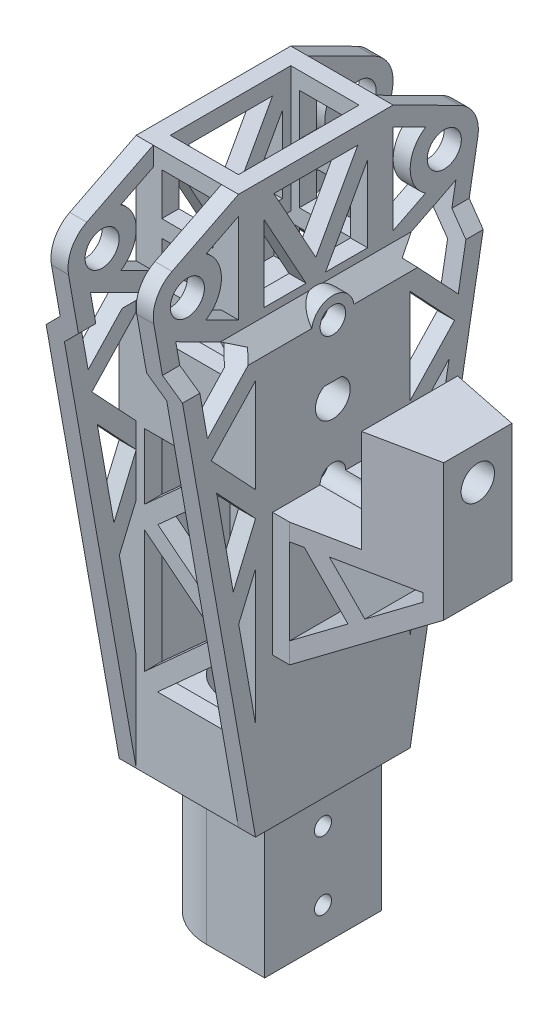
SolidWorks part; units mm, degrees
other "Markup1"
sketch "Sketch125" plane through (39.6875, -63.7385, 30.2705) normal (0.4776, -0.0046, 0.8786) x (0.8777, 0.0477, -0.4769)
material "Oynx"
ref_plane "Front Plane" through (0, 0, 0) normal (0, 0, 1) x (1, 0, 0)
ref_plane "Top Plane" through (0, 0, 0) normal (0, 1, 0) x (1, 0, 0)
ref_plane "Right Plane" through (0, 0, 0) normal (1, 0, 0) x (0, 0, -1)
sketch "Sketch1" plane through (0, 0, 0) normal (0, 1, 0) x (1, 0, 0)
  line L1 (-9.525, -14.3954) -> (9.525, -14.3954)
  line L2 (-9.525, -14.3954) -> (-9.525, 14.3954)
  line L3 (-9.525, 14.3954) -> (9.525, 14.3954)
  line L4 (9.525, -14.3954) -> (9.525, 14.3954)
  line L5 (-9.525, -14.3954) -> (9.525, 14.3954) construction
  line L6 (-9.525, 14.3954) -> (9.525, -14.3954) construction
  point P0 (0, 0)
  dimension "D1" = 28.7909
  dimension "D2" = 19.05
extrude "Boss-Extrude1" add sketch "Sketch1" along normal mid plane 127.4771 contours L3 L4 L1 L2
sketch "Sketch2" plane through (0, -63.7385, 0) normal (0, -1, 0) x (1, 0, 0)
  line L1 (-9.525, -9.525) -> (9.525, -9.525)
  line L2 (-9.525, -9.525) -> (-9.525, 9.525)
  line L3 (-9.525, 9.525) -> (9.525, 9.525)
  line L4 (9.525, -9.525) -> (9.525, 9.525)
  line L5 (-9.525, -9.525) -> (9.525, 9.525) construction
  line L6 (-9.525, 9.525) -> (9.525, -9.525) construction
  point P0 (0, 0)
  dimension "D1" = 19.05
extrude "Cut-Extrude1" cut sketch "Sketch2" against normal blind 25.4 flip side to cut contours L3 L4 L1 L2
sketch "Sketch30" plane through (0, 0, 0) normal (0, 0, 1) x (1, 0, 0)
  line L0 (9.525, -38.3385) -> (-9.525, -38.3385) construction
  line L1 (-9.525, 63.7385) -> (-12.7, 63.7385)
  line L2 (-9.525, 63.7385) -> (-9.525, -38.3385)
  line L3 (-9.525, -38.3385) -> (-12.7, -38.3385)
  line L4 (-12.7, 63.7385) -> (-12.7, -38.3385)
  line L6 (9.525, 63.7385) -> (12.7, 63.7385)
  line L7 (9.525, 63.7385) -> (9.525, -38.3385)
  line L8 (9.525, -38.3385) -> (12.7, -38.3385)
  line L9 (12.7, 63.7385) -> (12.7, -38.3385)
  dimension "D1" = 3.175
extrude "Boss-Extrude8" add sketch "Sketch30" along normal up to surface and the other way up to surface up to face at (0, 12.7, 14.3954) other way up to face at (0, 12.7, -14.3954)
sketch "Sketch115" plane through (0, -38.3385, 0) normal (0, -1, 0) x (1, 0, 0)
  line L1 (-10.8585, -10.8585) -> (10.8585, -10.8585)
  line L2 (-10.8585, -10.8585) -> (-10.8585, 10.8585)
  line L3 (-10.8585, 10.8585) -> (10.8585, 10.8585)
  line L4 (10.8585, -10.8585) -> (10.8585, 10.8585)
  line L5 (-10.8585, -10.8585) -> (10.8585, 10.8585) construction
  line L6 (-10.8585, 10.8585) -> (10.8585, -10.8585) construction
  line L11 (9.525, 9.525) -> (-9.525, 9.525)
  line L12 (-9.525, 9.525) -> (-9.525, -9.525)
  line L13 (-9.525, -9.525) -> (9.525, -9.525)
  line L14 (9.525, -9.525) -> (9.525, 9.525)
  line L15 (9.525, 9.525) -> (-9.525, 9.525)
  line L16 (-9.525, 9.525) -> (-9.525, -9.525)
  line L17 (-9.525, -9.525) -> (9.525, -9.525)
  line L18 (9.525, -9.525) -> (9.525, 9.525)
  point P0 (0, 0)
  dimension "D1" = 21.717
  dimension "D2" = 0
extrude "Boss-Extrude13" add sketch "Sketch115" along normal up to surface (25.4 mm away) up to face at (0, -63.7385, 0)
sketch "Sketch81" plane through (0, -63.7385, 0) normal (0, -1, 0) x (1, 0, 0)
  line L0 (10.8585, 10.8585) -> (-10.8585, 10.8585) construction
  line L1 (0, 10.8585) -> (-10.8585, 10.8585)
  line L8 (-10.8585, 10.8585) -> (-10.8585, 0)
  line L14 (-10.8585, 0) -> (-10.8585, -10.8585)
  line L15 (-10.8585, -10.8585) -> (0, -10.8585)
  arc A2 (0, 10.8585) -> (0, -10.8585) centre (0, 0) ccw
  arc A3 (0, -10.8585) -> (0, 10.8585) centre (0, 0) ccw construction
  line M22 (-10.8585, -10.8585) -> (10.8585, -10.8585)
  line M24 (10.8585, 10.8585) -> (-10.8585, 10.8585)
  line M25 (-10.8585, 10.8585) -> (-10.8585, -10.8585)
extrude "Cut-Extrude37" cut sketch "Sketch81" against normal up to surface (25.4 mm away) contours A2 M24 M25 | A2 M25 M22 region at (-8.4331, -63.7385, 8.4331) region at (-8.4331, -63.7385, -8.4331) up to face at (0, -38.3385, 0)
sketch "Sketch62" plane through (12.7, 0, 0) normal (1, 0, 0) x (0, 0, -1)
  line L0 (0, 25.1615) -> (0, -38.3385) construction
  line L1 (-14.3955, -38.3385) -> (14.3955, -38.3385) construction
  line L2 (1.651, 27.9475) -> (-1.651, 27.9475)
  arc A0 (-1.651, 27.9475) -> (1.651, 27.9475) centre (0, 25.1615) ccw
  dimension "D2" = 6.477
  dimension "D1" = 63.5
  dimension "D3" = 3.302
extrude "Cut-Extrude31_D-ShaftHole" cut sketch "Sketch62" against normal through all
sketch "Sketch22" plane through (0, -63.7385, 0) normal (0, -1, 0) x (1, 0, 0)
  line L6 (0, -7.6835) -> (7.6835, -7.6835)
  line L7 (7.6835, -7.6835) -> (7.6835, 7.6835)
  line L8 (7.6835, 7.6835) -> (0, 7.6835)
  line L9 (0, -7.6835) -> (7.6835, -7.6835)
  line L10 (7.6835, -7.6835) -> (7.6835, 7.6835)
  line L11 (7.6835, 7.6835) -> (0, 7.6835)
  arc A3 (0, 7.6835) -> (0, -7.6835) centre (0, 0) ccw
  arc A4 (0, 7.6835) -> (0, -7.6835) centre (0, 0) ccw
  dimension "D1" = 3.175
extrude "Cut-Extrude4_BottomHole" cut sketch "Sketch22" against normal blind 38.1
sketch "Sketch26" plane through (0, 0, 0) normal (1, 0, 0) x (0, 0, -1)
  line L0 (-14.3955, 63.7385) -> (-14.3955, -38.3385) construction
  line L1 (0, 65.1622) -> (0, -27.4319) construction
  line L2 (-14.3955, 63.7385) -> (-26.7765, 57.5038)
  line L3 (-14.3955, 39.926) -> (-29.6181, 47.5918) construction
  line L4 (-23.9205, 51.8323) -> (-14.3955, 51.8323) construction
  line L5 (-14.3955, 63.7385) -> (-14.3955, 51.8323) construction
  line L6 (-14.3955, 51.8323) -> (-14.3955, 39.926) construction
  line L7 (-14.3955, 43.4809) -> (-20.4368, 46.5232)
  line L8 (-17.4161, 45.002) -> (-18.8441, 42.1663) construction
  line L9 (-14.3955, 60.1837) -> (-20.4368, 57.1414)
  line L10 (-17.4161, 58.6626) -> (-18.8441, 61.4983) construction
  line L11 (-14.3955, 63.7385) -> (-14.3955, 60.1837)
  line L12 (-14.3955, 43.4809) -> (-14.3955, 39.926) construction
  line L13 (-30.1731, 50.7246) -> (-14.3955, -38.3385)
  line L14 (-14.3955, 43.4809) -> (-14.3955, -38.3385)
  line L15 (14.3955, 43.4809) -> (14.3955, 39.926) construction
  line L16 (17.4161, 58.6626) -> (18.8441, 61.4983) construction
  line L17 (17.4161, 45.002) -> (18.8441, 42.1663) construction
  line L18 (14.3955, 51.8323) -> (14.3955, 39.926) construction
  line L19 (14.3955, 63.7385) -> (14.3955, 51.8323) construction
  line L20 (23.9205, 51.8323) -> (14.3955, 51.8323) construction
  line L21 (14.3955, 39.926) -> (29.6181, 47.5918) construction
  line L22 (14.3955, 43.4809) -> (14.3955, -38.3385)
  line L23 (30.1731, 50.7246) -> (14.3955, -38.3385)
  line L24 (14.3955, 63.7385) -> (14.3955, 60.1837)
  line L25 (14.3955, 60.1837) -> (20.4368, 57.1414)
  line L26 (14.3955, 43.4809) -> (20.4368, 46.5232)
  line L27 (14.3955, 63.7385) -> (26.7765, 57.5038)
  arc A0 (-26.7765, 57.5038) -> (-30.1731, 50.7246) centre (-23.9205, 51.8323) ccw
  circle A1 centre (-23.9205, 51.8323) radius 3.175
  arc A2 (-20.4368, 46.5232) -> (-20.4368, 57.1414) centre (-23.9205, 51.8323) ccw
  arc A3 (20.4368, 46.5232) -> (20.4368, 57.1414) centre (23.9205, 51.8323) cw
  circle A4 centre (23.9205, 51.8323) radius 3.175
  arc A5 (26.7765, 57.5038) -> (30.1731, 50.7246) centre (23.9205, 51.8323) cw
  dimension "D3" = 6.35
  dimension "D4" = 12.7
  dimension "D1" = 11.9062
  dimension "D2" = 9.525
  dimension "D5" = 3.175
sketch "Sketch116" plane through (10.8585, 0, 0) normal (1, 0, 0) x (0, 0, -1)
  line L0 (0, -57.3885) -> (0, -44.6885) construction
  line L1 (0, -44.6885) -> (0, -38.3385) construction
  line L2 (-14.3955, -38.3385) -> (14.3955, -38.3385) construction
  line L3 (0, -57.3885) -> (0, -63.7385) construction
  line L4 (10.8585, -63.7385) -> (-10.8585, -63.7385) construction
  circle A0 centre (0, -44.6885) radius 1.5875
  circle A1 centre (0, -57.3885) radius 1.5875
  dimension "D2" = 3.175
  dimension "D1" = 12.7
extrude "Cut-Extrude65" cut sketch "Sketch116" against normal through all
extrude "Boss-Extrude3_\"Fins\"" add sketch "Sketch26" along normal up to surface (12.7 mm away) and the other way up to surface (12.7 mm away) contours L7 A2 L9 L11 L2 A0 L13 L14 A1 | A5 L27 L24 L25 A3 L26 L22 L23 A4 region at (0, 23.6902, 19.9871) region at (0, 23.6902, -19.9871) up to face at (12.7, 24.9352, 0) other way up to face at (-12.7, 24.9352, 0)
sketch "Sketch27" plane through (0, 63.7385, 0) normal (0, 1, 0) x (1, 0, 0)
  line L0 (-12.7, -14.3955) -> (12.7, -14.3955) construction
  line L1 (-6.35, -14.3955) -> (6.35, -14.3955)
  line L2 (-6.35, -14.3955) -> (-6.35, -30.2704)
  line L3 (-6.35, -30.2704) -> (6.35, -30.2704)
  line L4 (6.35, -14.3955) -> (6.35, -30.2704)
  line L5 (-12.7, -30.2704) -> (12.7, -30.2704) construction
  line L6 (-6.35, -22.3329) -> (-12.7, -22.333) construction
  line L7 (-12.7, -14.3955) -> (-12.7, -26.7765) construction
  line L8 (6.35, -22.3329) -> (12.7, -22.3329) construction
  line L9 (12.7, -26.7765) -> (12.7, -14.3955) construction
  line L10 (-12.7, 0) -> (12.7, 0) construction
  line L11 (-12.7, -14.3955) -> (-12.7, 14.3955) construction
  line L12 (12.7, -14.3955) -> (12.7, 14.3955) construction
  line L13 (6.35, 22.3329) -> (12.7, 22.3329) construction
  line L14 (-6.35, 22.3329) -> (-12.7, 22.333) construction
  line L15 (6.35, 14.3955) -> (6.35, 30.2704)
  line L16 (-6.35, 30.2704) -> (6.35, 30.2704)
  line L17 (-6.35, 14.3955) -> (-6.35, 30.2704)
  line L18 (-6.35, 14.3955) -> (6.35, 14.3955)
  dimension "D1" = 6.35
extrude "Cut-Extrude7" cut sketch "Sketch27" against normal through all
sketch "Sketch31" plane through (0, 0, 14.3954) normal (0, 0, 1) x (1, 0, 0)
  line L0 (-9.525, -38.3385) -> (-9.525, 37.1309)
  line L1 (-6.35, -38.3385) -> (-12.7, -38.3385) construction
  line L2 (-9.525, 37.1309) -> (-6.35, 40.3059)
  line L3 (-6.35, -38.3385) -> (-6.35, 50.7246) construction
  line L4 (-6.35, 40.3059) -> (-6.35, -38.3385)
  line L5 (-6.35, -38.3385) -> (-9.525, -38.3385)
  line L6 (6.35, -38.3385) -> (6.35, 40.3059)
  line L7 (6.35, 50.7246) -> (6.35, -38.3385) construction
  line L8 (6.35, 40.3059) -> (9.525, 37.1309)
  line L9 (9.525, 37.1309) -> (9.525, -38.3385)
  line L10 (12.7, -38.3385) -> (6.35, -38.3385) construction
  line L11 (9.525, -38.3385) -> (6.35, -38.3385)
  line L12 (9.525, 37.1309) -> (6.35, 37.1309) construction
  line L13 (-9.525, 37.1309) -> (-6.35, 37.1309) construction
  line L14 (-6.35, 40.3059) -> (6.35, 40.3059) construction
  dimension "D1" = 3.175
  dimension "D2" = 45
  dimension "D3" = 45
  dimension "D4" = 3.175
extrude "Cut-Extrude13" cut sketch "Sketch31" along normal through all
extrude "Cut-Extrude16" cut sketch "Sketch31<2>" against normal through all from surface starting at face at (0, 38.7882, -14.3954)
sketch "Sketch31<2>" plane through (0, 0, 14.3954) normal (0, 0, 1) x (1, 0, 0) same geometry as "Sketch31"
sketch "Sketch53" plane through (0, 0, 0) normal (0, 0, 1) x (1, 0, 0)
  line L0 (12.7, 38.446) -> (9.525, 41.621)
  line L1 (12.7, -38.3385) -> (12.7, 50.7246) construction
  line L2 (9.525, 41.621) -> (9.525, 63.7385)
  line L3 (6.35, 63.7385) -> (12.7, 63.7385) construction
  line L4 (9.525, 63.7385) -> (12.7, 63.7385)
  line L5 (12.7, 63.7385) -> (12.7, 38.446)
  line L6 (9.525, 37.1309) -> (6.35, 40.3059) construction
  line L7 (7.9375, 38.7184) -> (10.1826, 40.9635) construction
  line L8 (9.525, 52.6798) -> (6.35, 52.6798) construction
  line L9 (6.35, 57.5038) -> (6.35, 50.7246) construction
  line L10 (0, 47.881) -> (0, -47.881) construction
  line L11 (-9.525, 52.6798) -> (-6.35, 52.6798) construction
  line L12 (-7.9375, 38.7184) -> (-10.1826, 40.9635) construction
  line L13 (-12.7, 63.7385) -> (-12.7, 38.446)
  line L14 (-9.525, 63.7385) -> (-12.7, 63.7385)
  line L15 (-9.525, 41.621) -> (-9.525, 63.7385)
  line L16 (-12.7, 38.446) -> (-9.525, 41.621)
  dimension "D1" = 3.175
extrude "Cut-Extrude30" cut sketch "Sketch53" against normal through all both and the other way through all
sketch "Sketch54" plane through (0, 0, 0) normal (1, 0, 0) x (0, 0, -1)
  line L0 (-14.3955, 43.4809) -> (-14.3955, -38.3385) construction
  line L1 (-26.0875, 45.8635) -> (-14.3955, -20.1369) construction
  line L2 (-14.3955, -38.3385) -> (-27.9979, 38.446) construction
  line L3 (-20.2415, 12.8633) -> (-23.3678, 12.3095) construction
  line L4 (-26.0779, 45.809) -> (-14.3955, 39.926)
  line L5 (-20.4368, 46.5232) -> (-14.3955, 43.4809) construction
  line L6 (-17.4161, 45.002) -> (-18.8441, 42.1663) construction
  line L7 (-26.0779, 45.809) -> (-23.346, 30.3879)
  line L8 (-23.346, 30.3879) -> (-14.3955, 39.926)
  line L9 (-14.3955, 35.2862) -> (-22.6546, 26.4849)
  line L10 (-22.6546, 26.4849) -> (-14.3955, 17.6836)
  line L11 (-14.3955, 17.6836) -> (-14.3955, 35.2862)
  line L15 (-18.525, 30.8855) -> (-20.8403, 33.0582) construction
  line L18 (-14.3955, 13.0437) -> (-21.6413, 20.7653)
  line L20 (-18.0184, 16.9045) -> (-15.7031, 19.0771) construction
  line L21 (-26.0779, 45.809) -> (-26.7765, 46.1608) construction
  line L22 (0, 43.7979) -> (0, -43.7979) construction
  line L23 (26.0779, 45.809) -> (26.7765, 46.1608) construction
  line L24 (18.0184, 16.9045) -> (15.7031, 19.0771) construction
  line L25 (18.525, 30.8855) -> (20.8403, 33.0582) construction
  line L26 (17.4161, 45.002) -> (18.8441, 42.1663) construction
  line L27 (20.2415, 12.8633) -> (23.3678, 12.3095) construction
  line L28 (26.0875, 45.8635) -> (14.3955, -20.1369) construction
  line L29 (14.3955, 43.4809) -> (14.3955, -38.3385) construction
  line L31 (14.3955, 13.0437) -> (21.6413, 20.7653)
  line L33 (14.3955, 17.6836) -> (14.3955, 35.2862)
  line L34 (22.6546, 26.4849) -> (14.3955, 17.6836)
  line L35 (14.3955, 35.2862) -> (22.6546, 26.4849)
  line L36 (23.346, 30.3879) -> (14.3955, 39.926)
  line L37 (26.0779, 45.809) -> (23.346, 30.3879)
  line L38 (26.0779, 45.809) -> (14.3955, 39.926)
  line L39 (-21.6413, 20.7653) -> (-18.5479, 3.303)
  line L40 (-18.5479, 3.303) -> (-14.3955, 13.0437)
  line L41 (-14.3955, 4.9473) -> (-17.5346, -2.4166)
  line L42 (-14.3955, 4.9473) -> (-14.3955, -20.1369)
  line L43 (-14.3955, -20.1369) -> (-17.5346, -2.4166)
  line L44 (-16.4717, 8.1734) -> (-13.551, 6.9283) construction
  line L45 (14.3955, 13.0437) -> (18.5479, 3.303)
  line L46 (18.5479, 3.303) -> (21.6413, 20.7653)
  line L47 (14.3955, -20.1369) -> (17.5346, -2.4166)
  line L48 (17.5346, -2.4166) -> (14.3955, 4.9473)
  line L49 (14.3955, 4.9473) -> (14.3955, -20.1369)
  line L50 (15.965, 1.2653) -> (18.8857, 2.5104) construction
  circle A0 centre (-23.9205, 51.8323) radius 6.35 construction
  arc A1 (-20.4368, 46.5232) -> (-20.4368, 57.1414) centre (-23.9205, 51.8323) ccw construction
  circle A2 centre (23.9205, 51.8323) radius 6.35 construction
  dimension "D1" = 3.175
extrude "Cut-Extrude31_FrontSideCutouts" cut sketch "Sketch54" against normal through all both and the other way through all contours L7 L8 L4 | L10 L11 L9 | L37 L38 L36 | L35 L33 L34 | L31 | L43 L42 L41 | L48 L49 L47 | L18 L39 L40 region at (0, 38.7077, 21.2731) region at (0, 26.4849, 17.1485) region at (0, 12.3707, -18.1949) region at (0, 26.4849, -17.1485) region at (0, 38.7077, -21.2731) region at (0, -5.8688, 15.4418) region at (0, -5.8688, -15.4418)
sketch "Sketch75" plane through (0, 0, 14.3954) normal (0, 0, 1) x (1, 0, 0)
  line L0 (9.525, -38.3385) -> (9.525, 37.1309) construction
  line L7 (9.525, 37.1309) -> (6.7298, 39.926) construction
  line L8 (-9.525, 41.621) -> (9.525, 41.621) construction
  line L9 (-6.9512, 37.4597) -> (-8.0737, 38.5822) construction
  line L14 (-6.7298, 39.926) -> (-9.525, 37.1309) construction
  line L32 (-12.7, 38.446) -> (12.7, 38.446) construction
  line L62 (6.9512, 37.4597) -> (8.0737, 38.5822) construction
  line L63 (9.525, 37.1309) -> (6.35, 40.3059) construction
  line L64 (-4.7625, 51.0923) -> (4.7625, 51.0923) construction
  line L65 (-6.35, 60.5635) -> (6.35, 60.5635) construction
  line L66 (-6.35, 60.1837) -> (-6.35, 63.7385) construction
  line L67 (6.35, 63.7385) -> (6.35, 57.5038) construction
  line L68 (0, 60.5635) -> (0, 63.7385) construction
  line L69 (6.35, 63.7385) -> (-6.35, 63.7385) construction
  line L70 (0, 41.621) -> (0, 38.446) construction
  line L71 (-4.7625, 41.621) -> (-4.7625, 60.5635) construction
  line L72 (4.7625, 60.5635) -> (4.7625, 41.621) construction
  line L73 (-4.7625, 51.0923) -> (-6.35, 51.0923) construction
  line L74 (-6.35, 50.7246) -> (-6.35, 57.5038) construction
  line L75 (4.7625, 51.0923) -> (6.35, 51.0923) construction
  line L76 (6.35, 57.5038) -> (6.35, 50.7246) construction
  line L77 (-4.7625, 52.6798) -> (4.7625, 52.6798)
  line L82 (0, 52.6798) -> (0, 49.5048) construction
  line L85 (-6.35, 40.3059) -> (-9.525, 37.1309) construction
  line L86 (7.9375, 36.4733) -> (5.9648, 38.446)
  line L87 (5.9648, 38.446) -> (-5.9648, 38.446)
  line L89 (-5.9648, 38.446) -> (-7.9375, 36.4733)
  line L90 (7.9375, 36.4733) -> (7.9375, 33.099)
  line L91 (7.9375, 33.099) -> (-7.9375, 33.099)
  line L92 (-7.9375, 33.099) -> (-7.9375, 36.4733)
  line L93 (12.7, 33.099) -> (-12.7, 33.099) construction
  line L94 (12.7, -38.3385) -> (12.7, 38.446) construction
  line L95 (-12.7, -38.3385) -> (-12.7, 38.446) construction
  line L96 (4.7625, 49.5048) -> (-4.7625, 49.5048)
  line L113 (-9.525, 37.1309) -> (-9.525, -38.3385) construction
  line L117 (-4.7625, 52.6798) -> (-4.7625, 60.5635)
  line L118 (-4.7625, 60.5635) -> (4.7625, 60.5635)
  line L124 (12.7, 25.1615) -> (-12.7, 25.1615) construction
  line L125 (12.7, -38.3385) -> (12.7, 38.446) construction
  line L126 (-12.7, -38.3385) -> (-12.7, 38.446) construction
  line L127 (0, 25.1615) -> (0, -38.3385) construction
  line L128 (9.525, -38.3385) -> (-9.525, -38.3385) construction
  line L131 (4.7625, 60.5635) -> (4.7625, 52.6798)
  line L132 (4.7625, 49.5048) -> (4.7625, 41.621)
  line L133 (4.7625, 41.621) -> (-4.7625, 41.621)
  line L134 (-4.7625, 41.621) -> (-4.7625, 49.5048)
  point P62 (0, 51.0923)
  dimension "D2" = 63.5
  dimension "D3" = 7.9375
  dimension "D4" = 3.175
  dimension "D5" = 1.5875
  dimension "D10" = 1.5875
  dimension "D11" = 1.5875
  dimension "D12" = 3.175
sketch "Sketch79" plane through (0, 0, 0) normal (0, 0, 1) x (1, 0, 0)
  line L0 (6.35, 63.7385) -> (-6.35, 63.7385)
  line L1 (6.35, 63.7385) -> (6.35, 57.5038) construction
  line L2 (-6.35, 57.5038) -> (-6.35, 63.7385) construction
  line L3 (-6.35, 63.7385) -> (-6.35, 40.3059)
  line L4 (-6.35, 40.3059) -> (-9.525, 37.1309)
  line L5 (-9.525, 37.1309) -> (-9.525, 31.5115)
  line L6 (-9.525, 37.1309) -> (-9.525, -38.3385) construction
  line L7 (-9.525, 31.5115) -> (9.525, 31.5115)
  line L8 (9.525, -38.3385) -> (9.525, 37.1309) construction
  line L9 (9.525, 31.5115) -> (9.525, 37.1309)
  line L10 (9.525, 37.1309) -> (6.35, 40.3059)
  line L11 (6.35, 40.3059) -> (6.35, 63.7385)
  line L12 (0, 25.1615) -> (12.7, 25.1615) construction
  line L13 (12.7, -38.3385) -> (12.7, 38.446) construction
  line L14 (0, 25.1615) -> (-12.7, 25.1615) construction
  line L15 (9.525, 18.8115) -> (-9.525, 18.8115)
  line L16 (9.525, 18.8115) -> (9.525, -25.6385)
  line L17 (9.525, -25.6385) -> (-9.525, -25.6385)
  line L18 (-9.525, 18.8115) -> (-9.525, -25.6385)
  line L19 (-12.7, -38.3385) -> (-12.7, 38.446) construction
  line L21 (9.525, -38.3385) -> (-9.525, -38.3385) construction
  line L25 (0, 25.1615) -> (0, 18.8115) construction
  line L26 (0, 25.1615) -> (0, 31.5115) construction
  line L27 (6.35, 63.7385) -> (-6.35, 63.7385) construction
  line L28 (9.525, -38.3385) -> (9.525, 37.1309) construction
  dimension "D1" = 63.5
  dimension "D2" = 12.7
  dimension "D3" = 44.45
extrude "Cut-Extrude35" cut sketch "Sketch79" along normal offset from surface 3.175 and the other way offset from surface 3.175 up to face at (0, 24.372, 14.3955) other way up to face at (0, 24.372, -14.3955)
extrude "Cut-Extrude32_SideCutouts" cut sketch "Sketch75" against normal through all
sketch "Sketch83" plane through (0, 0, -14.3954) normal (0, 0, -1) x (-1, 0, 0)
  line L0 (0, 17.224) -> (0, -24.051) construction
  line L1 (-7.9375, 17.224) -> (7.9375, 17.224) construction
  line L2 (-7.9375, 17.224) -> (-7.9375, -24.051) construction
  line L3 (-7.9375, -24.051) -> (7.9375, -24.051) construction
  line L4 (7.9375, 17.224) -> (7.9375, -24.051) construction
  line L6 (9.525, 37.1309) -> (9.525, -38.3385) construction
  line L8 (-7.9375, 17.224) -> (7.9375, 2.8982) construction
  line L9 (7.9375, 2.8982) -> (-7.9375, -9.7253) construction
  line L10 (-7.9375, -9.7253) -> (7.9375, -24.051) construction
  line L11 (-7.9375, 15.0856) -> (5.4831, 2.9747)
  line L12 (5.4831, 2.9747) -> (-7.9375, -7.6971)
  line L13 (-5.5679, 17.224) -> (7.9375, 5.0365)
  line L14 (7.9375, 0.87) -> (-5.4831, -9.8018)
  line L15 (-5.4831, -9.8018) -> (7.9375, -21.9127)
  line L16 (-7.9375, -11.8636) -> (5.5679, -24.051)
  line L17 (-1.2272, 9.0302) -> (0.8999, 11.3873) construction
  line L18 (1.2272, -15.8573) -> (-0.8999, -18.2144) construction
  line L19 (1.2272, -4.4659) -> (-0.7489, -1.9808) construction
  line L20 (-5.5679, 17.224) -> (7.9375, 17.224)
  line L21 (7.9375, 17.224) -> (7.9375, 5.0365)
  line L22 (-7.9375, 15.0856) -> (-7.9375, -7.6971)
  line L23 (7.9375, 0.87) -> (7.9375, -21.9127)
  line L24 (-7.9375, -11.8636) -> (-7.9375, -24.051)
  line L25 (-7.9375, -24.051) -> (5.5679, -24.051)
  line L26 (0, -38.3385) -> (0, -24.051) construction
  line L27 (-9.525, -38.3385) -> (9.525, -38.3385) construction
  point P27 (-0.1636, 10.2087)
  point P30 (0.1636, -17.0358)
  point P33 (0.2391, -3.2234)
  dimension "D1" = 1.5875
  dimension "D2" = 3.175
  dimension "D3" = 3.175
  dimension "D4" = 3.175
  dimension "D5" = 12.7
  dimension "D6" = 14.2875
  dimension "D7" = 41.275
extrude "Cut-Extrude40" cut sketch "Sketch83" against normal through all
sketch "Sketch85" plane through (6.35, 0, 0) normal (1, 0, 0) x (0, 0, -1)
  line L0 (0, 25.1615) -> (0, 12.4615) construction
  line L1 (0, 25.1615) -> (0, 37.8615) construction
  circle A0 centre (0, 37.8615) radius 3.9688
  circle A1 centre (0, 12.4615) radius 3.9688
  arc A2 (-1.651, 27.9475) -> (1.651, 27.9475) centre (0, 25.1615) ccw construction
  dimension "D2" = 7.9375
  dimension "D1" = 25.4
extrude "Boss-Extrude9" add sketch "Sketch85" along normal up to next
sketch "Sketch87" plane through (12.7, 0, 0) normal (1, 0, 0) x (0, 0, -1)
  line L1 (0, 25.1615) -> (0, 37.8615) construction
  circle A0 centre (0, 37.8615) radius 3.9688
  arc A2 (-3.1266, 40.3059) -> (3.1266, 40.3059) centre (0, 37.8615) ccw construction
  arc A3 (-1.651, 27.9475) -> (1.651, 27.9475) centre (0, 25.1615) ccw construction
extrude "Boss-Extrude10" add sketch "Sketch87" against normal up to next
sketch "Sketch86" plane through (12.7, 0, 0) normal (1, 0, 0) x (0, 0, -1)
  line L0 (0, 25.1615) -> (0, 12.4615) construction
  line L1 (0, 25.1615) -> (0, 37.8615) construction
  circle A0 centre (0, 37.8615) radius 2.3812
  circle A1 centre (0, 12.4615) radius 2.3812
  arc A3 (-3.1266, 40.3059) -> (3.1266, 40.3059) centre (0, 37.8615) ccw construction
  dimension "D1" = 4.7625
extrude "Cut-Extrude41" cut sketch "Sketch86" against normal blind 3.175
sketch "Sketch88" plane through (12.7, 0, 0) normal (1, 0, 0) x (0, 0, -1)
  circle A0 centre (0, 12.4615) radius 1.5875
  circle A1 centre (0, 37.8615) radius 1.5875
  dimension "D1" = 3.175
extrude "Cut-Extrude42" cut sketch "Sketch88" against normal up to surface (6.35 mm away) up to face at (6.35, 47.0479, 0)
mirror "Mirror1" about plane through (0, 0, 0) normal (1, 0, 0) of "Boss-Extrude10", "Cut-Extrude41", "Cut-Extrude42", "Boss-Extrude9"
sketch "Sketch100" plane through (0, 0, 0) normal (1, 0, 0) x (0, 0, -1)
  line L0 (11.2205, 60.5635) -> (11.2205, 43.101) construction
  line L1 (11.2205, 43.101) -> (-11.2205, 43.101) construction
  line L2 (-11.2205, 43.101) -> (-11.2205, 60.5635) construction
  line L3 (-11.2205, 60.5635) -> (11.2205, 60.5635) construction
  line L4 (0, 63.7385) -> (0, 60.5635) construction
  line L5 (14.3955, 63.7385) -> (-14.3955, 63.7385) construction
  line L6 (9.633, 60.5635) -> (9.633, 43.101) construction
  line L7 (-11.2204, 51.8323) -> (-14.3955, 51.8323) construction
  line L8 (14.3955, 51.8323) -> (11.2205, 51.8323) construction
  line L9 (14.3955, 60.1837) -> (14.3954, 43.4809) construction
  line L10 (-14.3954, 60.1837) -> (-14.3955, 43.4809) construction
  line L11 (-9.633, 60.5635) -> (-9.633, 43.101) construction
  line L12 (-9.633, 51.8323) -> (-11.2204, 51.8323) construction
  line L13 (11.2205, 51.8323) -> (9.633, 51.8323) construction
  line L14 (9.633, 60.5635) -> (0, 43.101) construction
  line L15 (0, 43.101) -> (-9.633, 60.5635) construction
  line L16 (0, 43.101) -> (0, 60.5635) construction
  line L17 (7.8199, 60.5635) -> (0, 46.3877)
  line L18 (0, 46.3877) -> (-7.8199, 60.5635)
  line L19 (-9.633, 57.2769) -> (-1.813, 43.101)
  line L20 (1.813, 43.101) -> (9.633, 57.2769)
  line L21 (-5.723, 50.189) -> (-2.9429, 51.7226) construction
  line L22 (5.723, 50.189) -> (2.9429, 51.7226) construction
  line L23 (-1.813, 43.101) -> (-9.633, 43.101)
  line L24 (-9.633, 43.101) -> (-9.633, 57.2769)
  line L25 (1.813, 43.101) -> (9.633, 43.101)
  line L26 (9.633, 43.101) -> (9.633, 57.2769)
  line L27 (7.8199, 60.5635) -> (-7.8199, 60.5635)
  arc A0 (3.9255, 38.446) -> (-3.9255, 38.446) centre (0, 37.8615) ccw construction
  arc A1 (3.9255, 38.446) -> (-3.9255, 38.446) centre (0, 37.8615) ccw construction
  point P15 (-11.2205, 51.8323)
  point P39 (-4.333, 50.9558)
  dimension "D1" = 3.175
  dimension "D2" = 1.5875
extrude "Cut-Extrude53" cut sketch "Sketch100" against normal up to next and the other way up to next
sketch "Sketch101" plane through (0, 0, 0) normal (0, 0, 1) x (1, 0, 0)
  line L0 (12.7, 10.0802) -> (12.7, 14.8427) construction
  line L1 (12.7, 35.4802) -> (12.7, 40.2427) construction
  line L2 (12.7, 10.0802) -> (12.7, 14.8427) construction
  line L3 (12.7, 35.4802) -> (12.7, 40.2427) construction
  line L4 (12.7, 35.4802) -> (12.7, 14.8427) construction
  line L5 (12.7, 25.1615) -> (33.3375, 25.1615) construction
  line L6 (39.6875, 31.5115) -> (39.6875, 18.8115) construction
  line L7 (26.9875, 18.8115) -> (39.6875, 18.8115) construction
  line L8 (26.9875, 31.5115) -> (26.9875, 18.8115) construction
  line L9 (33.3375, 18.8115) -> (33.3375, 25.1615) construction
  line L10 (26.9875, 31.5115) -> (39.6875, 31.5115) construction
  line L11 (33.3375, 31.5115) -> (33.3375, 25.1615) construction
  line L12 (39.6875, 31.5115) -> (39.6875, 6.1115)
  line L13 (26.9875, 31.5115) -> (26.9875, 12.4615)
  line L14 (26.9875, 12.4615) -> (12.7, 12.4615)
  line L15 (12.7, -38.3385) -> (12.7, 38.446) construction
  line L16 (26.9875, 12.4615) -> (26.9875, 6.1115) construction
  line L17 (26.9875, 6.1115) -> (39.6875, 6.1115) construction
  line L18 (12.7, -10.5573) -> (15.875, -10.5573)
  line L19 (15.875, -10.5573) -> (39.6875, 6.1115)
  line L20 (26.9875, 31.5115) -> (39.6875, 31.5115)
  line L21 (12.7, -10.5573) -> (12.7, 12.4615)
  dimension "D1" = 20.6375
  dimension "D2" = 6.35
  dimension "D3" = 12.7
  dimension "D4" = 3.175
  dimension "D5" = 23.0187
extrude "Boss-Extrude11" add sketch "Sketch101" along normal mid plane 22.4409
sketch "Sketch102" plane through (39.6875, 0, 0) normal (1, 0, 0) x (0, 0, -1)
  circle A0 centre (0, 25.1615) radius 3.1115
  arc A1 (-1.651, 27.9475) -> (1.651, 27.9475) centre (0, 25.1615) ccw construction
  dimension "D1" = 6.223
extrude "Cut-Extrude54" cut sketch "Sketch102" against normal up to next
sketch "Sketch103" plane through (12.7, 0, 0) normal (1, 0, 0) x (0, 0, -1)
  circle A0 centre (0, 12.4615) radius 2.3812 construction
  circle A1 centre (0, 12.4615) radius 2.3812
extrude "Cut-Extrude55" cut sketch "Sketch103" along normal up to surface (14.2875 mm away) up to face at (26.9875, 28.273, 0)
sketch "Sketch104" plane through (0, 0, 0) normal (0, 0, 1) x (1, 0, 0)
  line L0 (15.875, 9.2865) -> (15.875, -6.6817)
  line L1 (15.875, -6.6817) -> (15.875, -6.6817)
  line L2 (15.875, -6.6817) -> (24.8932, -0.369)
  line L3 (36.5125, 7.7645) -> (36.5125, 9.2865)
  line L4 (36.5125, 28.3365) -> (30.1625, 28.3365) construction
  line L5 (30.1625, 18.8115) -> (30.1625, 12.4615) construction
  line L6 (30.1625, 9.2865) -> (22.01, 9.2865)
  line L7 (12.7, 12.4615) -> (12.7, -10.5573)
  line L8 (12.7, -10.5573) -> (15.875, -10.5573)
  line L9 (15.875, -10.5573) -> (39.6875, 6.1115)
  line L10 (39.6875, 6.1115) -> (39.6875, 31.5115)
  line L11 (39.6875, 31.5115) -> (26.9875, 31.5115)
  line L12 (26.9875, 31.5115) -> (26.9875, 12.4615)
  line L13 (26.9875, 12.4615) -> (12.7, 12.4615)
  line L14 (12.7, 12.4615) -> (12.7, -10.5573) construction
  line L15 (12.7, -10.5573) -> (15.875, -10.5573) construction
  line L16 (15.875, -10.5573) -> (39.6875, 6.1115) construction
  line L17 (39.6875, 6.1115) -> (39.6875, 31.5115) construction
  line L18 (39.6875, 31.5115) -> (26.9875, 31.5115) construction
  line L19 (26.9875, 31.5115) -> (26.9875, 12.4615) construction
  line L20 (26.9875, 12.4615) -> (12.7, 12.4615) construction
  line L21 (30.1625, 18.8115) -> (36.5125, 18.8115) construction
  line L22 (36.5125, 18.8115) -> (36.5125, 28.3365) construction
  line L23 (36.5125, 7.7645) -> (36.5125, 28.3365) construction
  line L24 (30.1625, 28.3365) -> (30.1625, 18.8115) construction
  line L25 (30.1625, 28.3365) -> (30.1625, 9.2865) construction
  line L26 (39.6875, 22.05) -> (39.6875, 28.273) construction
  line L27 (39.6875, 22.05) -> (39.6875, 28.273) construction
  line L28 (33.3375, 25.1615) -> (39.6875, 25.1615) construction
  line L29 (33.3375, 25.1615) -> (33.3375, 31.5115) construction
  line L30 (33.3375, 25.1615) -> (33.3375, 18.8115) construction
  line L31 (30.1625, 12.4615) -> (36.5125, 12.4615) construction
  line L32 (30.1625, 9.2865) -> (36.5125, 9.2865)
  line L33 (36.5125, 9.2865) -> (36.5125, 12.4615) construction
  line L34 (36.5125, 12.4615) -> (36.5125, 18.8115) construction
  line L35 (30.1625, 12.4615) -> (30.1625, 9.2865) construction
  line L36 (30.1625, 18.8115) -> (36.5125, 18.8115) construction
  line L37 (36.5125, 12.4615) -> (30.1625, 12.4615) construction
  line L38 (26.1938, 0.5414) -> (20.0722, 9.2865) construction
  line L39 (24.8932, -0.369) -> (18.1344, 9.2865)
  line L40 (27.4943, 1.4518) -> (22.01, 9.2865)
  line L41 (24.7521, 5.3691) -> (22.1511, 3.5484) construction
  line L42 (26.1938, 0.5414) -> (27.4943, 1.4518) construction
  line L43 (27.4943, 1.4518) -> (36.5125, 7.7645)
  line L44 (15.875, -6.6817) -> (36.5125, 7.7645) construction
  line L45 (24.8932, -0.369) -> (26.1938, 0.5414) construction
  line L46 (22.01, 9.2865) -> (20.0722, 9.2865) construction
  line L47 (18.1344, 9.2865) -> (15.875, 9.2865)
  line L48 (30.1625, 9.2865) -> (15.875, 9.2865) construction
  line L49 (20.0722, 9.2865) -> (18.1344, 9.2865) construction
  point P33 (23.4516, 4.4587)
  dimension "D1" = 0
  dimension "D2" = 3.175
extrude "Cut-Extrude56" cut sketch "Sketch104" against normal through all both and the other way through all
sketch "Sketch105" plane through (0, -10.5573, 0) normal (0, -1, 0) x (1, 0, 0)
  line L0 (39.6875, 0) -> (0, 0) construction
  line L1 (39.6875, 11.2204) -> (39.6875, -11.2204) construction
  line L2 (39.6875, 6.35) -> (39.6875, -6.35) construction
  line L3 (39.6875, 11.2204) -> (39.6875, 6.35) construction
  line L4 (39.6875, -6.35) -> (39.6875, -11.2204) construction
  line L5 (15.875, 11.2204) -> (39.6875, 11.2204)
  line L6 (39.6875, 11.2204) -> (39.6875, 6.35)
  line L7 (39.6875, 6.35) -> (15.875, 11.2204)
  line L8 (39.6875, -6.35) -> (15.875, -11.2204)
  line L9 (15.875, -11.2204) -> (39.6875, -11.2204)
  line L10 (39.6875, -11.2204) -> (39.6875, -6.35)
  dimension "D1" = 12.7
extrude "Cut-Extrude57" cut sketch "Sketch105" against normal through all
equation "\"D3@Sketch31\"=\"D2@Sketch31\""
equation "\"D1@Boss-Extrude1\"=5.0000000+0.018783in"
